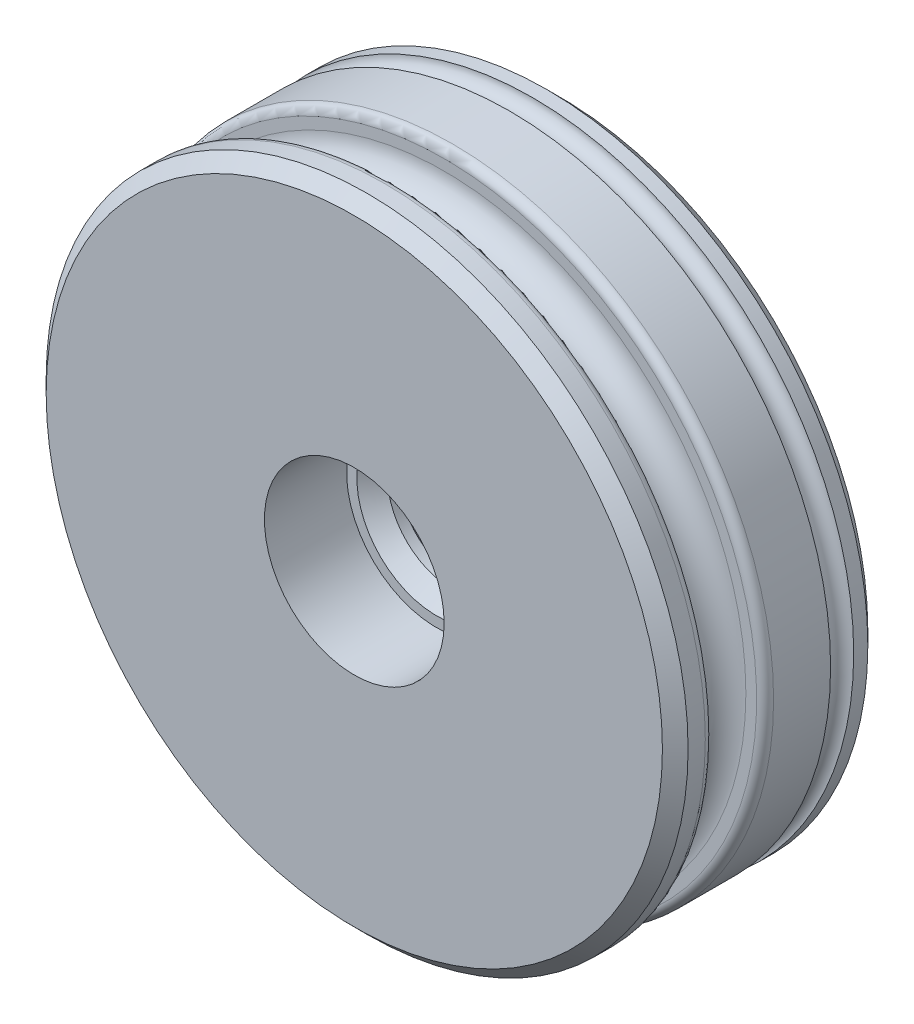
SolidWorks part; units mm, degrees
ref_plane "Front Plane" through (0, 0, 0) normal (0, 0, 1) x (1, 0, 0)
ref_plane "Top Plane" through (0, 0, 0) normal (0, 1, 0) x (1, 0, 0)
ref_plane "Right Plane" through (0, 0, 0) normal (1, 0, 0) x (0, 0, -1)
sketch "Sketch1" plane through (0, 0, 0) normal (0, 0, 1) x (1, 0, 0)
  circle A0 centre (0, 0) radius 12.5
  dimension "D1" = 25
extrude "Boss-Extrude1" add sketch "Sketch1" along normal blind 4
sketch "Sketch3" plane through (0, 0, 0) normal (1, 0, 0) x (0, 0, -1)
  line L0 (-4, 12.5) -> (-4, -12.5) construction
  line L2 (0, -12.5) -> (0, 12.5) construction
  line L3 (0, 12.5) -> (-4, 12.5) construction
  line L4 (-2.5, 11.75) -> (-2.5, 12.75)
  line L5 (-2.5, 12.75) -> (-0.5, 12.75)
  line L6 (-0.5, 12.75) -> (-0.5, 11.75)
  arc A0 (-2.5, 11.75) -> (-0.5, 11.75) centre (-1.5, 11.75) ccw
  dimension "D1" = 2
  dimension "D2" = 1.5
  dimension "D3" = 0.75
ref_axis "Axis1" through (0, 0, -0.35) along (0, 0, 1)
revolve "Cut-Revolve1" cut sketch "Sketch3" angle 360 about axis through (0, 0, -0.35) along (0, 0, 1)
sketch "Sketch2" plane through (0, 0, 4) normal (0, 0, 1) x (1, 0, 0)
  circle A0 centre (0, 0) radius 3.5
  dimension "D1" = 7
extrude "Cut-Extrude1" cut sketch "Sketch2" against normal blind 3.2
chamfer "Chamfer1" distance 0.5 angle 45 1 edges at (12.5, 0, 4)
sketch "Sketch4" plane through (0, 0, 0.8) normal (0, 0, 1) x (1, 0, 0)
  circle A0 centre (0, 0) radius 2.5
  dimension "D1" = 5
extrude "Cut-Extrude2" cut sketch "Sketch4" against normal through all
ref_axis "Axis2" through (0, 55, 4) along (0, -1, 0)
sketch "Sketch6" plane through (0, 0, 0) normal (1, 0, 0) x (0, 0, -1)
  line L0 (-4, 55) -> (-4, -55) construction
  line L1 (-4, 9) -> (-4, 11)
  line L2 (-2.5, 12.5) -> (-3.5, 12.5) construction
  arc A0 (-4, 11) -> (-4, 9) centre (-4, 10) ccw
  dimension "D1" = 2
  dimension "D2" = 2.5
revolve "Revolve1" [suppressed] add sketch "Sketch6" angle 360 about axis through (0, 55, 4) along (0, -1, 0)
chamfer "Chamfer2" distance 0.6 angle 45 1 edges at (2.5, 0, 0.8)
pattern_circular "CirPattern1" [suppressed] count 15 over 360 about axis through (0, 0, -0.35) along (0, 0, 1) reverse direction yes of bodies 110
mirror "Mirror2" about plane through (0, 0, 0) normal (0, 0, 1) of "Cut-Extrude2", "Chamfer1", "Cut-Extrude1", "Boss-Extrude1", "Chamfer2"
sketch "Sketch7" plane through (0, 0, 0) normal (1, 0, 0) x (0, 0, -1)
  line L0 (3.5, 12.5) -> (-0.5, 12.5) construction
  line L1 (3.5, -12.5) -> (3.5, 12.5) construction
  circle A0 centre (2.5, 12.5) radius 0.45
  dimension "D1" = 0.9
  dimension "D2" = 1
revolve "Cut-Revolve3" cut sketch "Sketch7" angle 360 about axis through (0, 0, -0.35) along (0, 0, 1)
fillet "Fillet1" radius 0.33 2 edges at (12.5, 0, 2.5) (-12.5, 0, 0.5)
